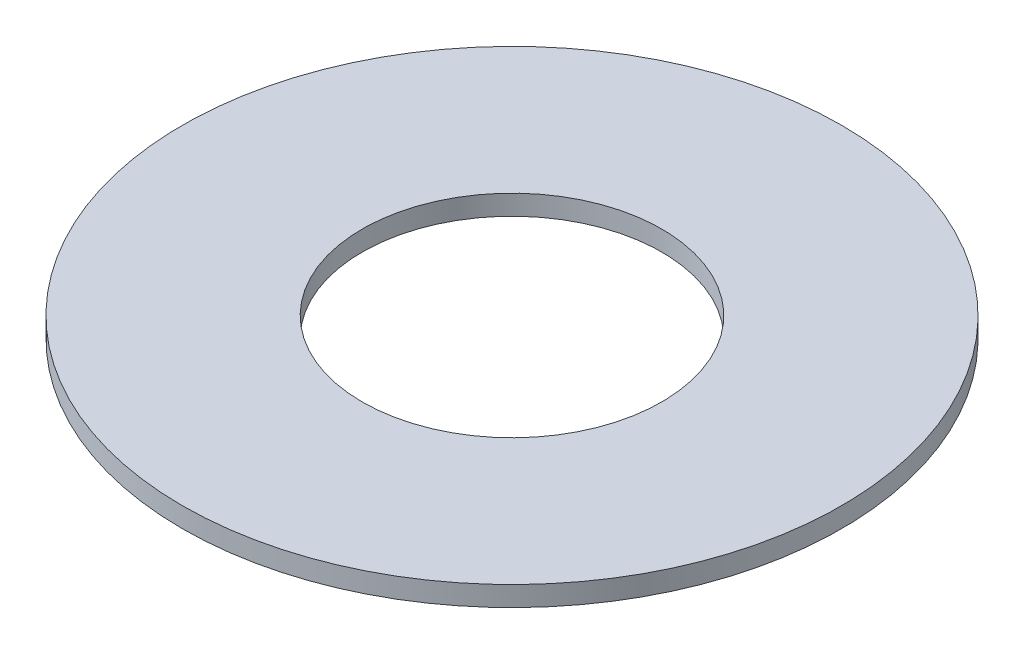
SolidWorks part; units mm, degrees
ref_plane "Front Plane" through (0, 0, 0) normal (0, 0, 1) x (1, 0, 0)
ref_plane "Top Plane" through (0, 0, 0) normal (0, 1, 0) x (1, 0, 0)
ref_plane "Right Plane" through (0, 0, 0) normal (1, 0, 0) x (0, 0, -1)
sketch "Sketch1" plane through (0, 0, 0) normal (0, 1, 0) x (1, 0, 0)
  circle A0 centre (0, 0) radius 82.5
  dimension "FLANGE_OD" = 165
extrude "Boss-Extrude1" add sketch "Sketch1" along normal blind 5
sketch "Sketch2" plane through (0, 0, 0) normal (0, 1, 0) x (1, 0, 0)
  circle A0 centre (0, 0) radius 37.5
  dimension "BORE_D" = 75
extrude "Cut-Extrude1" cut sketch "Sketch2" along normal through all
sketch "Sketch3" plane through (0, 5, 0) normal (0, 1, 0) x (1, 0, 0)
  circle A0 centre (0, 0) radius 25.565 construction
  circle A1 centre (-25.565, 0) radius 3.5792
  dimension "BOLT_D" = 7.1585
  dimension "BOLT_PCD" = 51.13
extrude "Cut-Extrude2" cut sketch "Sketch3" against normal blind 4.4771 rebuild error yes
pattern_circular "CirPattern1" count 3 over 360 rebuild error yes
